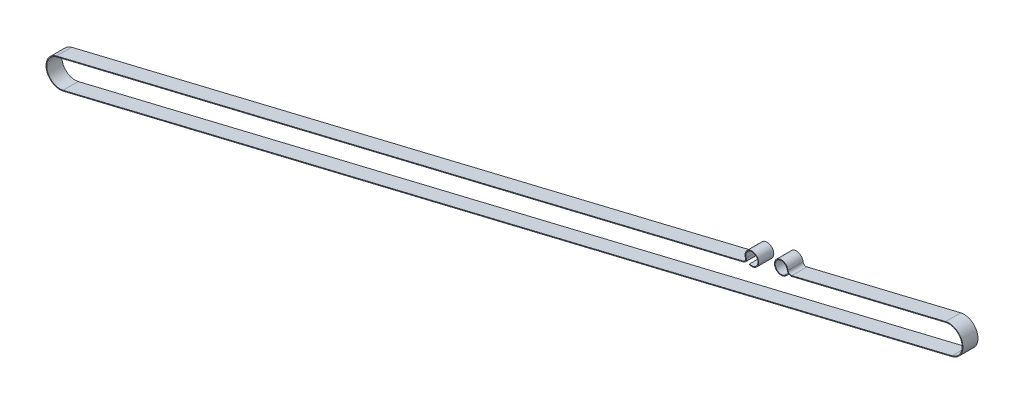
SolidWorks part; units mm, degrees
ref_plane "Спереди" through (0, 0, 0) normal (0, 0, 1) x (1, 0, 0)
ref_plane "Сверху" through (0, 0, 0) normal (0, 1, 0) x (1, 0, 0)
ref_plane "Справа" through (0, 0, 0) normal (1, 0, 0) x (0, 0, -1)
ref_axis "ОсьX" through (-88.99, 0, 0) along (1, 0, 0)
ref_axis "ОсьZ" through (0, 55, 0) along (0, -1, 0)
ref_axis "ОсьY" through (0, 0, -88.99) along (0, 0, 1)
sketch "Эскиз1" plane through (0, 0, 0) normal (0, 0, 1) x (1, 0, 0)
  line L0 (1172.137, 300.834) -> (968.4623, 251.6882)
  line L1 (958.2417, 281.626) -> (899.9156, 267.5522) construction
  line L2 (1180.3467, 266.8105) -> (4.1049, -17.0118)
  line L3 (904.4725, 236.2477) -> (-4.1049, 17.0118)
  arc A0 (-1.5, 17.4356) -> (-3.0638, 17.2297) centre (0, 0) ccw construction
  arc A1 (-4.1049, 17.0118) -> (4.1049, -17.0118) centre (0, 0) ccw
  arc A2 (1181.0285, 300.6549) -> (1179.4935, 301.0175) centre (1176.2419, 283.8222) ccw construction
  arc A3 (1180.3467, 266.8105) -> (1172.137, 300.834) centre (1176.2419, 283.8222) ccw
  circle A4 centre (915.5007, 245.5953) radius 8 construction
  arc A5 (912.4918, 238.1827) -> (907.9924, 242.834) centre (915.5007, 245.5953) ccw
  circle A6 centre (954.3848, 254.9779) radius 8 construction
  arc A7 (962.3261, 255.9445) -> (960.443, 249.7531) centre (954.3848, 254.9779) ccw
  arc A8 (907.9924, 242.834) -> (904.4725, 236.2477) centre (903.2997, 241.1082) cw
  arc A9 (962.3261, 255.9445) -> (968.4623, 251.6882) centre (967.2895, 256.5487) ccw
  point P33 (912.4918, 238.1827)
  dimension "D1" = 5
  dimension "D2" = 5
extrude "Вытянуть-Тонкостенный1" add sketch "Эскиз1" along normal blind 20 thin thin type one direction wall 1
